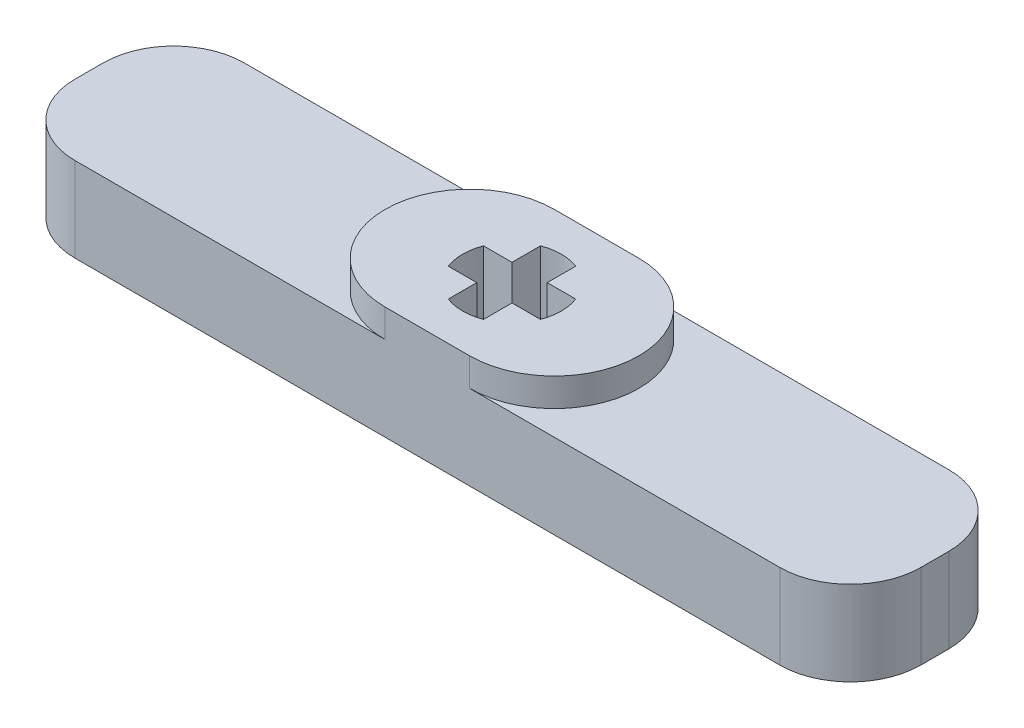
SolidWorks part; units mm, degrees
ref_plane "Płaszczyzna przednia" through (0, 0, 0) normal (0, 0, 1) x (1, 0, 0)
ref_plane "Płaszczyzna górna" through (0, 0, 0) normal (0, 1, 0) x (1, 0, 0)
ref_plane "Płaszczyzna prawa" through (0, 0, 0) normal (1, 0, 0) x (0, 0, -1)
sketch "Sketch1" plane through (0, 0, 0) normal (0, 1, 0) x (1, 0, 0)
  line L1 (-25, -6) -> (25, -6)
  line L2 (-30, -1) -> (-30, 1)
  line L3 (-25, 6) -> (25, 6)
  line L4 (30, -1) -> (30, 1)
  line L5 (-30, -6) -> (30, 6) construction
  line L6 (-30, 6) -> (30, -6) construction
  arc A0 (25, 6) -> (30, 1) centre (25, 1) cw
  arc A1 (25, -6) -> (30, -1) centre (25, -1) ccw
  arc A2 (-25, -6) -> (-30, -1) centre (-25, -1) cw
  arc A3 (-30, 1) -> (-25, 6) centre (-25, 1) cw
  point P0 (0, 0)
  dimension "D3" = 5
  dimension "D1" = 60
  dimension "D2" = 12
extrude "Boss-Extrude1" add sketch "Sketch1" along normal blind 6
sketch "Sketch2" plane through (0, 6, 0) normal (0, 1, 0) x (1, 0, 0)
  line L0 (0, 0) -> (-3, 0) construction
  line L1 (0, 0) -> (3, 0) construction
  line L2 (-3, 6) -> (3, 6)
  line L3 (-3, -6) -> (3, -6)
  arc A2 (3, -6) -> (3, 6) centre (3, 0) ccw
  arc A4 (-3, 6) -> (-3, -6) centre (-3, 0) ccw
extrude "Boss-Extrude2" add sketch "Sketch2" along normal blind 2
sketch "Sketch3" plane through (0, 8, 0) normal (0, 1, 0) x (1, 0, 0)
  line L0 (0, -3.5) -> (0, 3.5) construction
  line L1 (-3.5, 0) -> (3.5, 0) construction
  line L2 (2.7725, 0) -> (2.7725, 1.25) construction
  line L3 (2.7725, 0) -> (2.7725, -1.25) construction
  line L4 (0, 3.0635) -> (1.25, 3.0635) construction
  line L5 (0, 3.0635) -> (-1.25, 3.0635) construction
  line L6 (1.25, 3.2692) -> (1.25, 1.25)
  line L7 (-1.25, 3.2692) -> (-1.25, 1.25)
  line L8 (3.2692, 1.25) -> (1.25, 1.25)
  line L9 (3.2692, -1.25) -> (1.25, -1.25)
  line L10 (-1.25, -1.25) -> (-3.2692, -1.25)
  line L11 (-1.25, -1.25) -> (-1.25, -3.2692)
  line L12 (-1.25, 1.25) -> (-3.2692, 1.25)
  line L13 (1.25, -1.25) -> (1.25, -3.2692)
  circle A3 centre (0, 0) radius 3.5
extrude "Cut-Extrude1" cut sketch "Sketch3" against normal blind 5 contours L9 A3 L8 L6 L7 L12 L10 L11 L13 region at (0, 8, 0)
